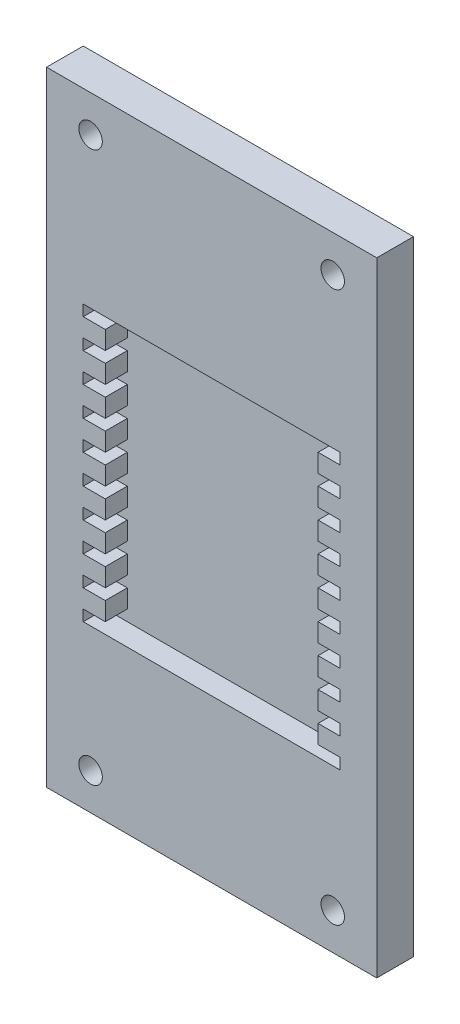
SolidWorks part; units mm, degrees
ref_plane "Ebene vorne" through (0, 0, 0) normal (0, 0, 1) x (1, 0, 0)
ref_plane "Ebene oben" through (0, 0, 0) normal (0, 1, 0) x (1, 0, 0)
ref_plane "Ebene rechts" through (0, 0, 0) normal (1, 0, 0) x (0, 0, -1)
sketch "Skizze1" plane through (0, 0, 0) normal (0, 0, 1) x (1, 0, 0)
  line L1 (0, 0) -> (45, 0)
  line L2 (0, 0) -> (0, 85)
  line L3 (0, 85) -> (45, 85)
  line L4 (45, 0) -> (45, 85)
  dimension "D1" = 45
  dimension "D2" = 85
extrude "Aufsatz-Linear austragen1" add sketch "Skizze1" along normal blind 5
sketch "Skizze6" plane through (0, 0, 5) normal (0, 0, 1) x (1, 0, 0)
  line L0 (0, 85) -> (0, 0) construction
  line L1 (45, 85) -> (0, 85) construction
  line L2 (45, 0) -> (45, 85) construction
  line L3 (0, 0) -> (45, 0) construction
  circle A0 centre (6, 80) radius 1.6
  circle A1 centre (39, 80) radius 1.6
  circle A2 centre (39, 5) radius 1.6
  circle A3 centre (6, 5) radius 1.6
  dimension "D8" = 6
  dimension "D9" = 3.2
  dimension "D10" = 3.2
  dimension "D11" = 3.2
  dimension "D12" = 3.2
  dimension "D1" = 6
  dimension "D2" = 5
  dimension "D3" = 5
  dimension "D4" = 6
  dimension "D5" = 5
  dimension "D6" = 6
  dimension "D7" = 5
extrude "Schnitt-Linear austragen2" cut sketch "Skizze6" against normal blind 3
sketch "Skizze7" plane through (0, 0, 5) normal (0, 0, 1) x (1, 0, 0)
  line L0 (45, 85) -> (0, 85) construction
  line L1 (5, 59.55) -> (40, 59.55)
  line L2 (5, 59.55) -> (5, 58.05)
  line L3 (5, 58.05) -> (40, 58.05)
  line L4 (40, 59.55) -> (40, 58.05)
  line L5 (45, 0) -> (45, 85) construction
  line L7 (5, 55.55) -> (40, 55.55)
  line L8 (5, 55.55) -> (5, 54.05)
  line L9 (5, 54.05) -> (40, 54.05)
  line L10 (40, 55.55) -> (40, 54.05)
  line L11 (5, 51.55) -> (40, 51.55)
  line L12 (5, 51.55) -> (5, 50.05)
  line L13 (5, 50.05) -> (40, 50.05)
  line L14 (40, 51.55) -> (40, 50.05)
  line L15 (5, 47.55) -> (40, 47.55)
  line L16 (5, 47.55) -> (5, 46.05)
  line L17 (5, 46.05) -> (40, 46.05)
  line L18 (40, 47.55) -> (40, 46.05)
  line L19 (5, 43.55) -> (40, 43.55)
  line L20 (5, 43.55) -> (5, 42.05)
  line L21 (5, 42.05) -> (40, 42.05)
  line L22 (40, 43.55) -> (40, 42.05)
  line L23 (5, 39.55) -> (40, 39.55)
  line L24 (5, 39.55) -> (5, 38.05)
  line L25 (5, 38.05) -> (40, 38.05)
  line L26 (40, 39.55) -> (40, 38.05)
  line L27 (5, 35.55) -> (40, 35.55)
  line L28 (5, 35.55) -> (5, 34.05)
  line L29 (5, 34.05) -> (40, 34.05)
  line L30 (40, 35.55) -> (40, 34.05)
  line L31 (5, 31.55) -> (40, 31.55)
  line L32 (5, 31.55) -> (5, 30.05)
  line L33 (5, 30.05) -> (40, 30.05)
  line L34 (40, 31.55) -> (40, 30.05)
  line L35 (5, 27.55) -> (40, 27.55)
  line L36 (5, 27.55) -> (5, 26.05)
  line L37 (5, 26.05) -> (40, 26.05)
  line L38 (40, 27.55) -> (40, 26.05)
  line L39 (5, 23.55) -> (40, 23.55)
  line L40 (5, 23.55) -> (5, 22.05)
  line L41 (5, 22.05) -> (40, 22.05)
  line L42 (40, 23.55) -> (40, 22.05)
  dimension "D1" = 25.45
  dimension "D2" = 1.5
  dimension "D3" = 5
  dimension "D4" = 35
  dimension "D5" = 2.5
  dimension "D6" = 1.5
  dimension "D7" = 2.5
  dimension "D8" = 1.5
  dimension "D9" = 2.5
  dimension "D10" = 1.5
  dimension "D11" = 2.5
  dimension "D12" = 1.5
  dimension "D13" = 2.5
  dimension "D14" = 1.5
  dimension "D15" = 2.5
  dimension "D16" = 1.5
  dimension "D17" = 2.5
  dimension "D18" = 1.5
  dimension "D19" = 2.5
  dimension "D20" = 1.5
  dimension "D21" = 2.5
  dimension "D22" = 1.5
extrude "Schnitt-Linear austragen3" cut sketch "Skizze7" against normal blind 10
sketch "Skizze8" plane through (0, 0, 5) normal (0, 0, 1) x (1, 0, 0)
  line L0 (40, 59.55) -> (5, 59.55) construction
  line L1 (8, 59.55) -> (37, 59.55)
  line L2 (8, 59.55) -> (8, 22.05)
  line L3 (8, 22.05) -> (37, 22.05)
  line L4 (37, 59.55) -> (37, 22.05)
  line L5 (5, 22.05) -> (40, 22.05) construction
  line L6 (40, 58.05) -> (40, 59.55) construction
  line L7 (5, 43.55) -> (5, 42.05) construction
  dimension "D1" = 3
  dimension "D2" = 3
extrude "Schnitt-Linear austragen4" cut sketch "Skizze8" against normal blind 10
sketch "Skizze9" plane through (0, 0, 0) normal (0, 0, -1) x (-1, 0, 0)
  line L1 (-41.3422, 60.8413) -> (-3.2909, 60.8413)
  line L2 (-41.3422, 60.8413) -> (-41.3422, 20.0732)
  line L3 (-41.3422, 20.0732) -> (-3.2909, 20.0732)
  line L4 (-3.2909, 60.8413) -> (-3.2909, 20.0732)
extrude "Aufsatz-Linear austragen2" add sketch "Skizze9" against normal blind 2
